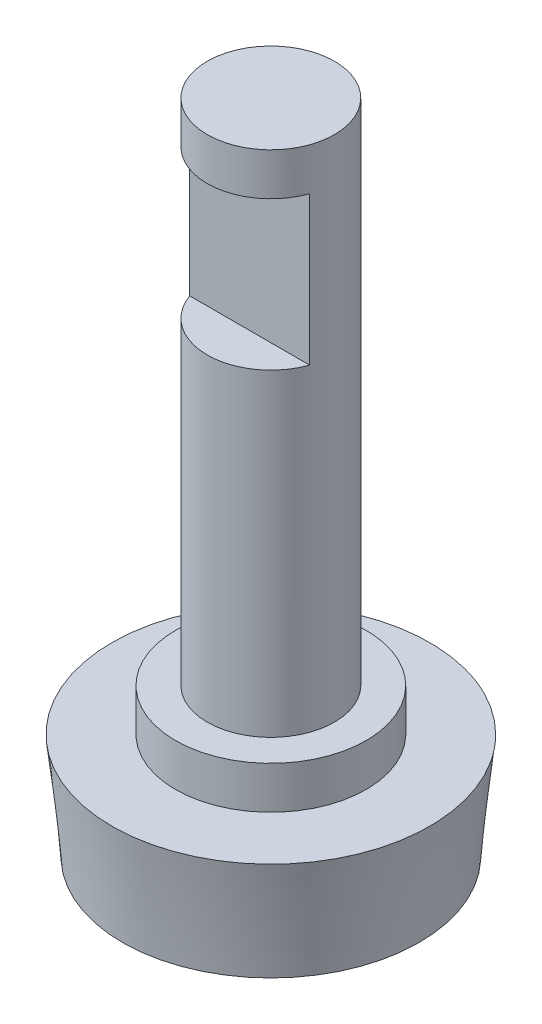
SolidWorks part; units mm, degrees
other "Markup1"
sketch "Sketch6" plane through (4.5039, 15.5, 4.2208) normal (0.4835, 0.0302, 0.8748) x (-0.4254, 0.8816, 0.2047)
ref_plane "Ön Düzlem" through (0, 0, 0) normal (0, 0, 1) x (1, 0, 0)
ref_plane "Üst Düzlem" through (0, 0, 0) normal (0, 1, 0) x (1, 0, 0)
ref_plane "Sağ Düzlem" through (0, 0, 0) normal (1, 0, 0) x (0, 0, -1)
sketch "Sketch1" plane through (0, 0, 0) normal (0, 1, 0) x (1, 0, 0)
  circle A0 centre (0, 0) radius 3.5
  dimension "7" = 7
ref_plane "Plane1" through (0, 2.5, 0) normal (0, 1, 0) x (1, 0, 0)
sketch "Sketch2" plane through (0, 2.5, 0) normal (0, 1, 0) x (1, 0, 0)
  circle A0 centre (0, 0) radius 3.75
  point P3 (-3.75, 0)
  dimension "D1" = 7.5
loft "Loft1" add profiles "Sketch1", "Sketch2" connector at (-1.4503, 0, 3.1854) connector at (-2.1927, 2.5, 3.0421)
sketch "Sketch3" plane through (0, 2.5, 0) normal (0, 1, 0) x (1, 0, 0)
  circle A0 centre (0, 0) radius 2.25
  dimension "D1" = 4.5
extrude "Boss-Extrude1" add sketch "Sketch3" along normal blind 1
sketch "Sketch4" plane through (0, 3.5, 0) normal (0, 1, 0) x (1, 0, 0)
  circle A0 centre (0, 0) radius 1.5
  dimension "D1" = 3
extrude "Boss-Extrude2" add sketch "Sketch4" along normal blind 12
ref_plane "Plane2" through (0, 14.5, 0) normal (0, 1, 0) x (1, 0, 0)
sketch "Sketch5" plane through (0, 14.5, 0) normal (0, 1, 0) x (1, 0, 0)
  line L0 (-1.4142, -0.5) -> (1.4142, -0.5)
  line L1 (0, -1.5) -> (0, -0.5) construction
  arc A0 (-1.4142, -0.5) -> (1.4142, -0.5) centre (0, 0) ccw
  dimension "D1" = 3
  dimension "D2" = 1
extrude "Cut-Extrude1" cut sketch "Sketch5" against normal blind 3.5
ref_plane "Plane3" through (-3.75, 0, 0) normal (1, 0, 0) x (0, 0, -1)
